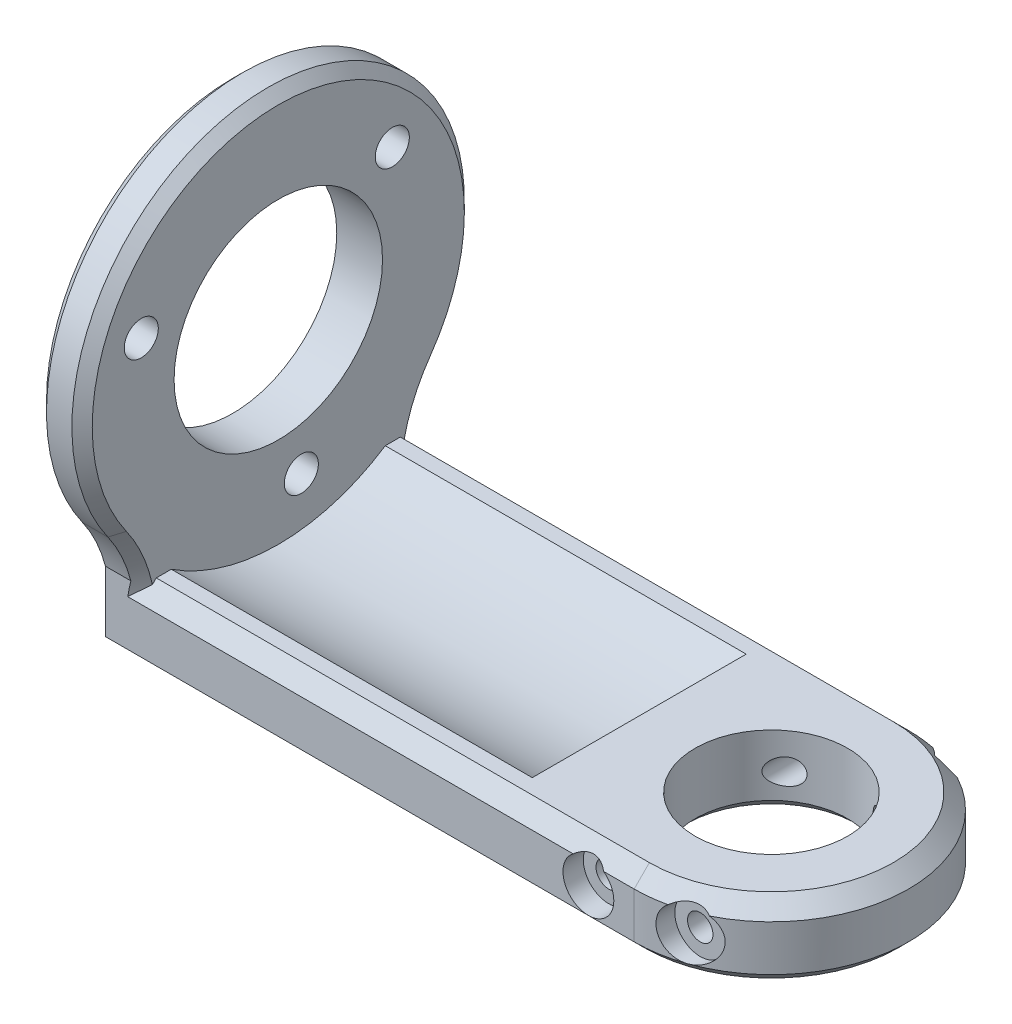
SolidWorks part; units mm, degrees
ref_plane "Alzado" through (0, 0, 0) normal (0, 0, 1) x (1, 0, 0)
ref_plane "Planta" through (0, 0, 0) normal (0, 1, 0) x (1, 0, 0)
ref_plane "Vista lateral" through (0, 0, 0) normal (1, 0, 0) x (0, 0, -1)
sketch "Croquis1" plane through (0, 0, 0) normal (0, 1, 0) x (1, 0, 0)
  line L0 (0, 13.5) -> (-53, 13.5)
  line L1 (0, -13.5) -> (-53, -13.5)
  line L2 (-53, 13.5) -> (-53, -13.5)
  circle A0 centre (0, 0) radius 7.5
  arc A1 (0, -13.5) -> (0, 13.5) centre (0, 0) ccw
  dimension "D1" = 15
  dimension "D2" = 6
  dimension "D3" = 53
extrude "Saliente-Extruir1" add sketch "Croquis1" along normal blind 7
sketch "Croquis2" plane through (-53, 0, 0) normal (-1, 0, 0) x (0, 0, 1)
  line L0 (-13.5, 0) -> (13.5, 0) construction
  circle A0 centre (0, 23) radius 19.3
  circle A1 centre (0, 23) radius 10.25
  point P5 (0, 0)
  dimension "D1" = 38.6
  dimension "D2" = 20.5
  dimension "D3" = 23
extrude "Saliente-Extruir2" add sketch "Croquis2" against normal blind 4.5
sketch "Croquis3" plane through (-48.5, 0, 0) normal (1, 0, 0) x (0, 0, -1)
  circle A0 centre (0, 23) radius 19.15
  dimension "D1" = 38.3
extrude "Cortar-Extruir1" cut sketch "Croquis3" along normal blind 35.5
fillet "Redondeo1" radius 15 2 edges at (-50.75, 7, -10.7931) (-50.75, 7, 10.7931)
sketch "Croquis5" plane through (0, 0, 0) normal (0, 0, 1) x (1, 0, 0)
  line L0 (0, 10.6911) -> (0, -3.8391) construction
  circle A0 centre (-4.5, 3.5) radius 1.25
  circle A1 centre (4.5, 3.5) radius 1.25
  dimension "D1" = 2.5
  dimension "D2" = 4.5
extrude "Cortar-Extruir2" cut sketch "Croquis5" against normal through all both and the other way through all
sketch "Croquis6" plane through (-53, 0, 0) normal (-1, 0, 0) x (0, 0, 1)
  line L0 (-11.2131, 32.0884) -> (-2.2642, 8.7449) construction
  line L1 (-2.2642, 8.7449) -> (13.4774, 28.1666) construction
  line L2 (13.4774, 28.1666) -> (-11.2131, 32.0884) construction
  circle A0 centre (0, 23) radius 14.4338 construction
  circle A1 centre (-2.2642, 8.7449) radius 1.675
  circle A2 centre (13.4774, 28.1666) radius 1.675
  circle A3 centre (-11.2131, 32.0884) radius 1.675
  dimension "D1" = 3.35
  dimension "D2" = 25
extrude "Cortar-Extruir3" cut sketch "Croquis6" against normal through all
sketch "Croquis7" plane through (-53, 0, 0) normal (-1, 0, 0) x (0, 0, 1)
  circle A0 centre (13.4774, 28.1666) radius 2.925
  circle A1 centre (-2.2642, 8.7449) radius 2.925
  circle A2 centre (-11.2131, 32.0884) radius 2.925
  dimension "D1" = 5.85
extrude "Cortar-Extruir4" cut sketch "Croquis7" against normal blind 2
sketch "Croquis8" plane through (0, 0, 13.5) normal (0, 0, 1) x (1, 0, 0)
  circle A0 centre (4.5, 3.5) radius 2.5
  circle A1 centre (-4.5, 3.5) radius 2.5
  dimension "D1" = 5
extrude "Cortar-Extruir5" cut sketch "Croquis8" against normal blind 2
sketch "Croquis9" plane through (0, 0, -13.5) normal (0, 0, -1) x (-1, 0, 0)
  line L1 (4.5, 6.5888) -> (1.825, 5.0444)
  line L2 (1.825, 5.0444) -> (1.825, 1.9556)
  line L3 (1.825, 1.9556) -> (4.5, 0.4112)
  line L4 (4.5, 0.4112) -> (7.175, 1.9556)
  line L5 (7.175, 1.9556) -> (7.175, 5.0444)
  line L6 (7.175, 5.0444) -> (4.5, 6.5888)
  line L7 (-4.5, 6.5888) -> (-7.175, 5.0444)
  line L8 (-7.175, 5.0444) -> (-7.175, 1.9556)
  line L9 (-7.175, 1.9556) -> (-4.5, 0.4112)
  line L10 (-4.5, 0.4112) -> (-1.825, 1.9556)
  line L11 (-1.825, 1.9556) -> (-1.825, 5.0444)
  line L12 (-1.825, 5.0444) -> (-4.5, 6.5888)
  circle A0 centre (4.5, 3.5) radius 2.675 construction
  circle A1 centre (-4.5, 3.5) radius 2.675 construction
  dimension "D1" = 5.35
extrude "Cortar-Extruir6" cut sketch "Croquis9" against normal blind 4
chamfer "Chaflán1" distance 1 angle 45 8 edges at (-48.5, 9.533, 14.4119) (-48.5, 9.533, -14.4119) (-48.5, 42.3, 0) (-53, 3.5, 13.5) (-53, 3.5, -13.5) (-53, 9.533, 14.4119) (-53, 9.533, -14.4119) (-53, 42.3, 0)
chamfer "Chaflán2" distance 1 angle 45 1 edges at (0, 0, 7.5)
chamfer "Chaflán4" distance 1.5 angle 45 3 edges at (-24.75, 7, -13.5) (13.5, 7, 0) (-24.75, 7, 13.5)
chamfer "Chaflán5" distance 1 angle 45 3 edges at (-26, 0, -13.5) (13.5, 0, 0) (-26, 0, 13.5)
chamfer "Chaflán6" distance 1 angle 45 1 edges at (-53, 0, 0)
